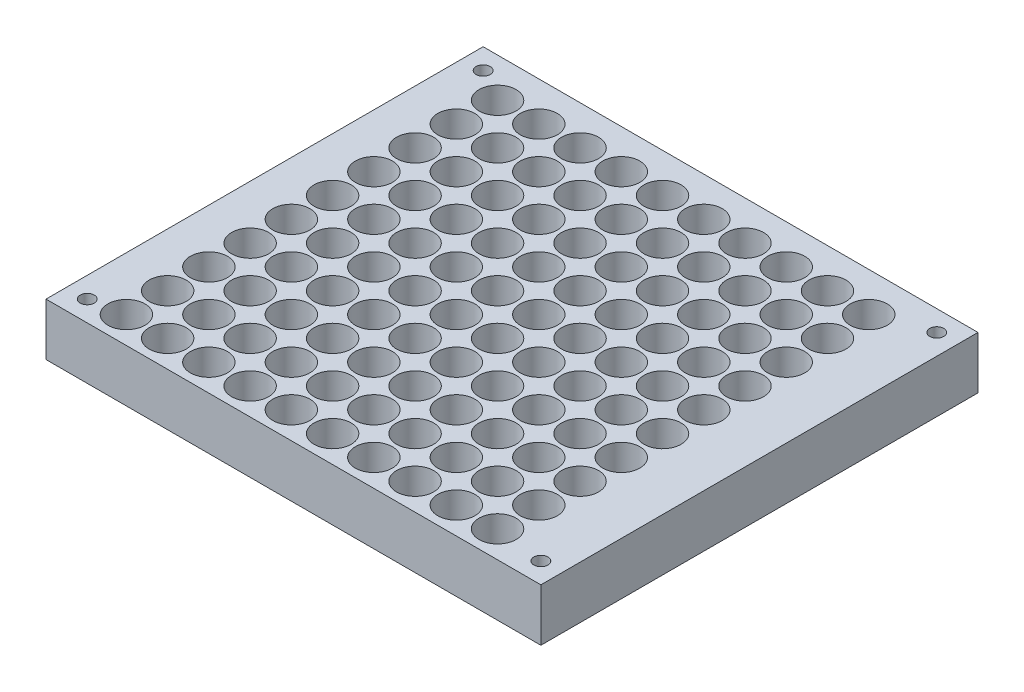
SolidWorks part; units mm, degrees
ref_plane "Front Plane" through (0, 0, 0) normal (0, 0, 1) x (1, 0, 0)
ref_plane "Top Plane" through (0, 0, 0) normal (0, 1, 0) x (1, 0, 0)
ref_plane "Right Plane" through (0, 0, 0) normal (1, 0, 0) x (0, 0, -1)
sketch "Sketch1" plane through (0, 0, 0) normal (0, 1, 0) x (1, 0, 0)
  line L0 (115, 101) -> (5, 101) construction
  line L1 (0, 0) -> (120, 0)
  line L2 (0, 0) -> (0, 106)
  line L3 (0, 106) -> (120, 106)
  line L4 (120, 0) -> (120, 106)
  line L6 (115, 101) -> (115, 5) construction
  circle A17 centre (13, 36.5) radius 4.5
  circle A18 centre (23, 36.5) radius 4.5
  circle A19 centre (13, 6.5) radius 4.5
  circle A28 centre (5, 5) radius 1.7
  circle A29 centre (5, 101) radius 1.7
  circle A30 centre (115, 101) radius 1.7
  circle A31 centre (115, 5) radius 1.7
  circle A32 centre (23, 6.5) radius 4.5
  circle A33 centre (33, 6.5) radius 4.5
  circle A34 centre (23, 16.5) radius 4.5
  circle A35 centre (33, 16.5) radius 4.5
  circle A36 centre (23, 26.5) radius 4.5
  circle A37 centre (33, 26.5) radius 4.5
  circle A38 centre (13, 16.5) radius 4.5
  circle A39 centre (13, 26.5) radius 4.5
  circle A40 centre (33, 36.5) radius 4.5
  circle A41 centre (13, 46.5) radius 4.5
  circle A42 centre (23, 46.5) radius 4.5
  circle A43 centre (33, 46.5) radius 4.5
  circle A44 centre (13, 56.5) radius 4.5
  circle A45 centre (23, 56.5) radius 4.5
  circle A46 centre (33, 56.5) radius 4.5
  circle A47 centre (13, 66.5) radius 4.5
  circle A48 centre (23, 66.5) radius 4.5
  circle A49 centre (33, 66.5) radius 4.5
  circle A50 centre (13, 76.5) radius 4.5
  circle A51 centre (23, 76.5) radius 4.5
  circle A52 centre (33, 76.5) radius 4.5
  circle A53 centre (13, 86.5) radius 4.5
  circle A54 centre (23, 86.5) radius 4.5
  circle A55 centre (33, 86.5) radius 4.5
  circle A56 centre (13, 96.5) radius 4.5
  circle A57 centre (23, 96.5) radius 4.5
  circle A58 centre (33, 96.5) radius 4.5
  circle A59 centre (43, 6.5) radius 4.5
  circle A60 centre (53, 6.5) radius 4.5
  circle A61 centre (63, 6.5) radius 4.5
  circle A62 centre (73, 6.5) radius 4.5
  circle A63 centre (83, 6.5) radius 4.5
  circle A64 centre (93, 6.5) radius 4.5
  circle A65 centre (103, 6.5) radius 4.5
  circle A66 centre (43, 16.5) radius 4.5
  circle A67 centre (53, 16.5) radius 4.5
  circle A68 centre (63, 16.5) radius 4.5
  circle A69 centre (73, 16.5) radius 4.5
  circle A70 centre (83, 16.5) radius 4.5
  circle A71 centre (93, 16.5) radius 4.5
  circle A72 centre (103, 16.5) radius 4.5
  circle A73 centre (43, 26.5) radius 4.5
  circle A74 centre (53, 26.5) radius 4.5
  circle A75 centre (63, 26.5) radius 4.5
  circle A76 centre (73, 26.5) radius 4.5
  circle A77 centre (83, 26.5) radius 4.5
  circle A78 centre (93, 26.5) radius 4.5
  circle A79 centre (103, 26.5) radius 4.5
  circle A80 centre (43, 36.5) radius 4.5
  circle A81 centre (53, 36.5) radius 4.5
  circle A82 centre (63, 36.5) radius 4.5
  circle A83 centre (73, 36.5) radius 4.5
  circle A84 centre (83, 36.5) radius 4.5
  circle A85 centre (93, 36.5) radius 4.5
  circle A86 centre (103, 36.5) radius 4.5
  circle A87 centre (43, 46.5) radius 4.5
  circle A88 centre (53, 46.5) radius 4.5
  circle A89 centre (63, 46.5) radius 4.5
  circle A90 centre (73, 46.5) radius 4.5
  circle A91 centre (83, 46.5) radius 4.5
  circle A92 centre (93, 46.5) radius 4.5
  circle A93 centre (103, 46.5) radius 4.5
  circle A94 centre (43, 56.5) radius 4.5
  circle A95 centre (53, 56.5) radius 4.5
  circle A96 centre (63, 56.5) radius 4.5
  circle A97 centre (73, 56.5) radius 4.5
  circle A98 centre (83, 56.5) radius 4.5
  circle A99 centre (93, 56.5) radius 4.5
  circle A100 centre (103, 56.5) radius 4.5
  circle A101 centre (43, 66.5) radius 4.5
  circle A102 centre (53, 66.5) radius 4.5
  circle A103 centre (63, 66.5) radius 4.5
  circle A104 centre (73, 66.5) radius 4.5
  circle A105 centre (83, 66.5) radius 4.5
  circle A106 centre (93, 66.5) radius 4.5
  circle A107 centre (103, 66.5) radius 4.5
  circle A108 centre (43, 76.5) radius 4.5
  circle A109 centre (53, 76.5) radius 4.5
  circle A110 centre (63, 76.5) radius 4.5
  circle A111 centre (73, 76.5) radius 4.5
  circle A112 centre (83, 76.5) radius 4.5
  circle A113 centre (93, 76.5) radius 4.5
  circle A114 centre (103, 76.5) radius 4.5
  circle A115 centre (43, 86.5) radius 4.5
  circle A116 centre (53, 86.5) radius 4.5
  circle A117 centre (63, 86.5) radius 4.5
  circle A118 centre (73, 86.5) radius 4.5
  circle A119 centre (83, 86.5) radius 4.5
  circle A120 centre (93, 86.5) radius 4.5
  circle A121 centre (103, 86.5) radius 4.5
  circle A122 centre (43, 96.5) radius 4.5
  circle A123 centre (53, 96.5) radius 4.5
  circle A124 centre (63, 96.5) radius 4.5
  circle A125 centre (73, 96.5) radius 4.5
  circle A126 centre (83, 96.5) radius 4.5
  circle A127 centre (93, 96.5) radius 4.5
  circle A128 centre (103, 96.5) radius 4.5
  point P7 (115, 53)
  point P9 (60, 101)
  point P10 (60, 106)
  point P20 (120, 53)
  dimension "D5" = 110
  dimension "D6" = 96
  dimension "D3" = 9
  dimension "D8" = 3.4
  dimension "D1" = 120
  dimension "D2" = 106
  dimension "D4" = 8
  dimension "D7" = 1.5
  dimension "D9" = 10
  dimension "D10" = 10
extrude "Boss-Extrude1" add sketch "Sketch1" along normal blind 12.7 contours L1 L4 L3 L2 A39 A36 A34 region at (1.6011, 0, -53)
equation "\"o\"= 10mm"
equation "\"P\"= 10"
